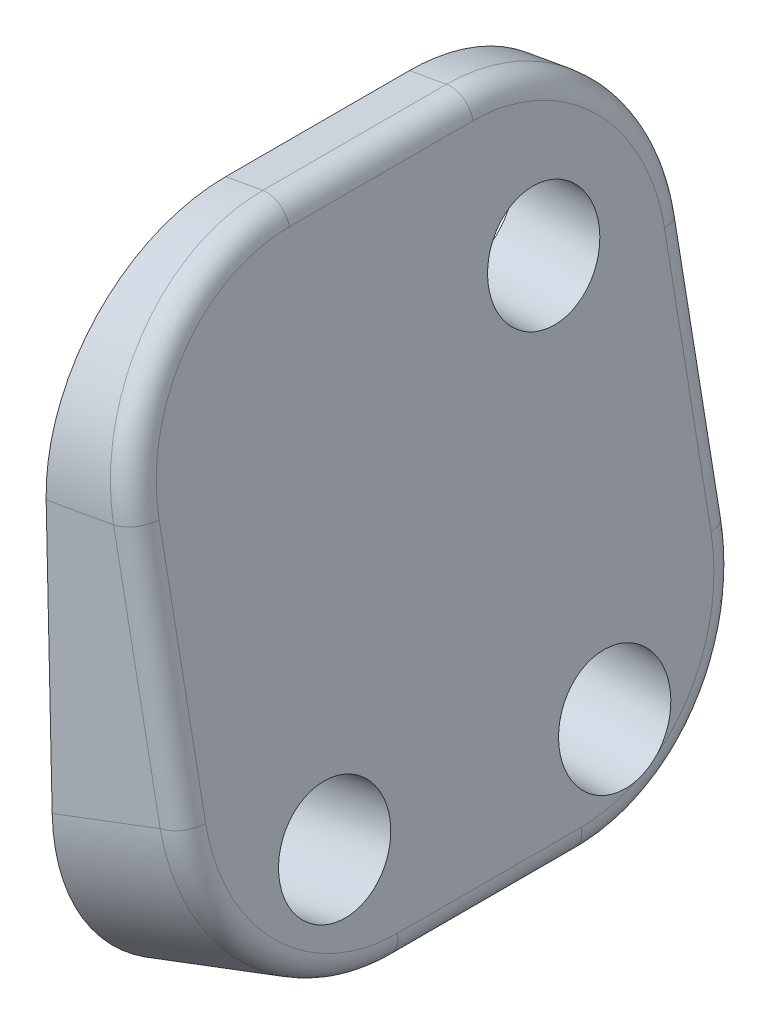
SolidWorks part; units mm, degrees
ref_plane "Front Plane" through (0, 0, 0) normal (0, 0, 1) x (1, 0, 0)
ref_plane "Top Plane" through (0, 0, 0) normal (0, 1, 0) x (1, 0, 0)
ref_plane "Right Plane" through (0, 0, 0) normal (1, 0, 0) x (0, 0, -1)
sketch "Sketch1" plane through (0, 0, 0) normal (0, 0, 1) x (1, 0, 0)
  line L0 (-5.5593, -2.1024) -> (-6.0621, 20.3359)
  line L2 (0, 0) -> (-5.5593, -2.1024)
  line L5 (-16.5204, 18.4775) -> (-4.0147, 20.6998) construction
  line L6 (-6.0621, 20.3359) -> (-4.0147, 20.6998)
  line L8 (-4.0147, 20.6998) -> (0, 0)
  line L9 (-6.7275, 50.0245) -> (-4.3089, -57.8984) construction
  line L13 (-12.06, -3.4695) -> (-1.4899, -1.2466) construction
  line L14 (-4.3089, -57.8984) -> (-6.7275, 50.0245) construction
  point P3 (-0.1453, -0.0954)
  point P4 (-0.1453, 0)
  point P6 (-0.1453, 0)
  point P8 (0, 0)
  point P10 (-5.7334, -1.2046)
  point P13 (0, 0)
  point P16 (-5.7376, -1.0196)
extrude "Boss-Extrude1" add sketch "Sketch1" along normal mid plane 19.05
sketch "Sketch6" plane through (-5.6036, -0.1256, 0) normal (-0.9997, -0.0224, 0) x (0, 0, 1)
  line L0 (-4.7625, 15.5947) -> (-4.7625, 20.4666) construction
  line L1 (9.525, 20.4666) -> (-9.525, 20.4666) construction
  line L2 (-4.7625, 2.8947) -> (-4.7625, -1.9773) construction
  line L3 (9.525, -1.9773) -> (-9.525, -1.9773) construction
  line L4 (-9.525, 20.4666) -> (-9.525, -1.9773) construction
  circle A0 centre (-4.7625, 2.8947) radius 1.905
  circle A1 centre (-4.7625, 15.5947) radius 1.905
  point P10 (0, 0)
  point P11 (-5.4784, 2.2086)
  dimension "D2" = 3.81
  dimension "D1" = 12.7
  dimension "D3" = 4.7625
extrude "Cut-Extrude2" cut sketch "Sketch6" against normal through all
sketch "Sketch8" plane through (0, 0, 0) normal (0.9817, 0.1904, 0) x (0, 0, -1)
  circle A0 centre (-4.7625, 3.7355) radius 1.905
  dimension "D1" = 3.81
extrude "Cut-Extrude3" cut sketch "Sketch8" against normal through all
fillet "Fillet1" radius 6.35 4 edges at (-2.7796, -1.0512, 9.525) (-2.7796, -1.0512, -9.525) (-5.0384, 20.5178, -9.525) (-5.0384, 20.5178, 9.525)
fillet "Fillet2" radius 0.7937 8 edges at (-4.0147, 20.6998, 0) (-3.6605, 18.8737, -7.6651) (-2.0161, 10.3951, -9.525) (-0.3593, 1.8525, -7.6651) (0, 0, 0) (-0.3593, 1.8525, 7.6651) (-2.0161, 10.3951, 9.525) (-3.6605, 18.8737, 7.6651)
